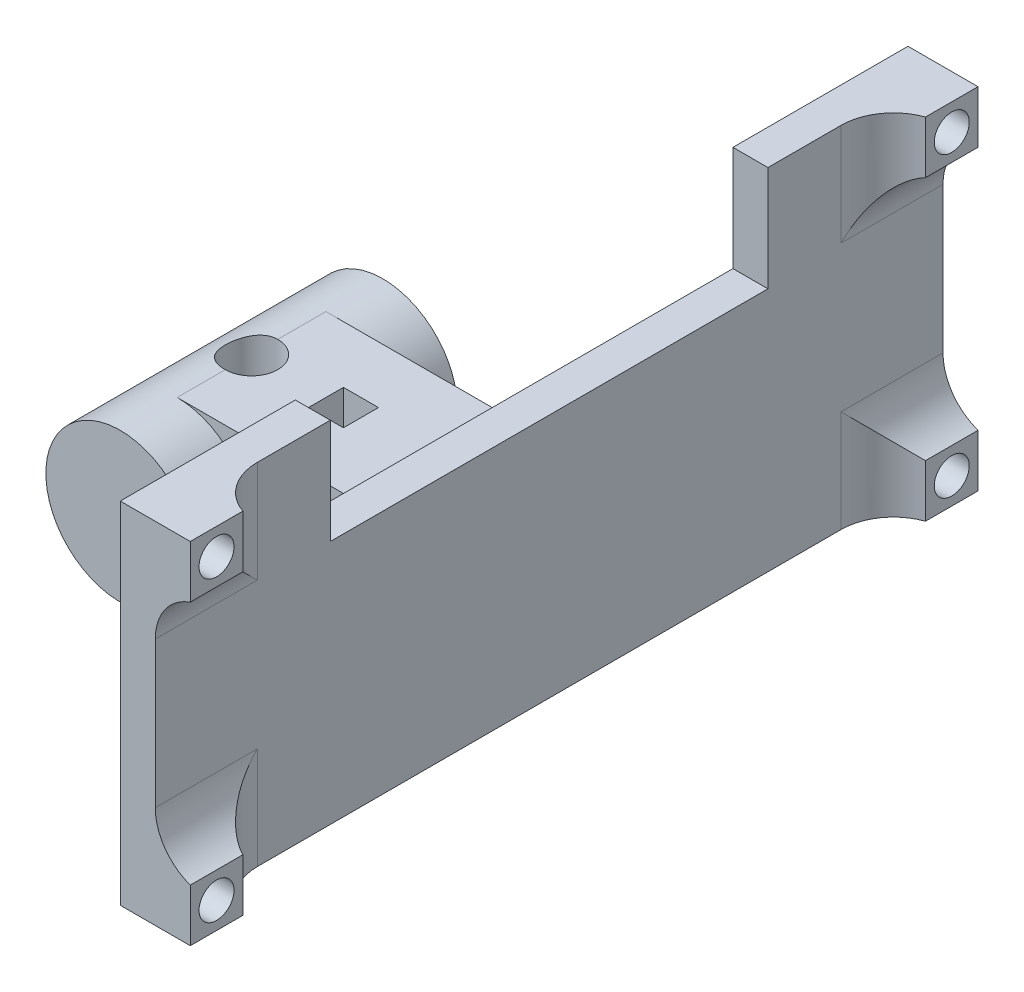
SolidWorks part; units mm, degrees
ref_plane "Front Plane" through (0, 0, 0) normal (0, 0, 1) x (1, 0, 0)
ref_plane "Top Plane" through (0, 0, 0) normal (0, 1, 0) x (1, 0, 0)
ref_plane "Right Plane" through (0, 0, 0) normal (1, 0, 0) x (0, 0, -1)
sketch "Sketch1" plane through (0, 0, 0) normal (0, 0, 1) x (1, 0, 0)
  circle A0 centre (0, 0) radius 4.25
  dimension "D1" = 8.5
extrude "Boss-Extrude1" add sketch "Sketch1" along normal mid plane 15
sketch "Sketch2" plane through (0, 0, 0) normal (1, 0, 0) x (0, 0, -1)
  line L0 (7.5, 4.25) -> (-7.5, 4.25) construction
  line L1 (7.5, 4.25) -> (-7.5, 4.25) construction
  line L3 (-4.25, -4.25) -> (4.25, -4.25)
  line L4 (-4.25, -4.25) -> (-4.25, 4.25)
  line L5 (-4.25, 4.25) -> (4.25, 4.25)
  line L6 (4.25, -4.25) -> (4.25, 4.25)
  line L7 (-4.25, -4.25) -> (4.25, 4.25) construction
  line L8 (-4.25, 4.25) -> (4.25, -4.25) construction
  point P0 (0, 0)
  dimension "D1" = 8.5
extrude "Boss-Extrude2" add sketch "Sketch2" along normal blind 15
sketch "Sketch3" plane through (15, 0, 0) normal (1, 0, 0) x (0, 0, -1)
  line L0 (-4.25, -4.25) -> (4.25, -4.25) construction
  line L1 (-22.5, -4.25) -> (22.5, -4.25)
  line L2 (-22.5, -4.25) -> (-22.5, 15.75)
  line L3 (-22.5, 15.75) -> (22.5, 15.75)
  line L4 (22.5, -4.25) -> (22.5, 15.75)
  point P6 (0, 15.75)
  dimension "D1" = 45
  dimension "D2" = 20
extrude "Boss-Extrude3" add sketch "Sketch3" along normal blind 4
sketch "Sketch4" plane through (19, 0, 0) normal (1, 0, 0) x (0, 0, -1)
  line L0 (-22.5, 5.75) -> (22.5, 5.75) construction
  line L1 (-22.5, 15.75) -> (-22.5, -4.25) construction
  line L2 (22.5, -4.25) -> (22.5, 15.75) construction
  line L3 (0, 15.75) -> (0, -4.25) construction
  line L4 (22.5, 15.75) -> (-22.5, 15.75) construction
  line L5 (-22.5, -4.25) -> (22.5, -4.25) construction
  circle A0 centre (-21, 14.25) radius 1
  circle A1 centre (-21, -2.75) radius 1
  circle A2 centre (21, -2.75) radius 1
  circle A3 centre (21, 14.25) radius 1
  dimension "D1" = 2
  dimension "D2" = 17
  dimension "D3" = 42
extrude "Cut-Extrude1" cut sketch "Sketch4" against normal through all
sketch "Sketch5" plane through (19, 0, 0) normal (1, 0, 0) x (0, 0, -1)
  line L0 (-19.5, 15.75) -> (19.5, 15.75)
  line L1 (-22.5, 15.75) -> (-19.5, 15.75)
  line L2 (-22.5, 15.75) -> (-22.5, 12.75)
  line L3 (-22.5, 12.75) -> (-19.5, 12.75)
  line L4 (-19.5, 15.75) -> (-19.5, 12.75)
  line L5 (-22.5, -4.25) -> (-19.5, -4.25)
  line L6 (-22.5, -4.25) -> (-22.5, -1.25)
  line L7 (-22.5, -1.25) -> (-19.5, -1.25)
  line L8 (-19.5, -4.25) -> (-19.5, -1.25)
  line L9 (22.5, -4.25) -> (19.5, -4.25)
  line L10 (22.5, -4.25) -> (22.5, -1.25)
  line L11 (22.5, -1.25) -> (19.5, -1.25)
  line L12 (19.5, -4.25) -> (19.5, -1.25)
  line L13 (22.5, 15.75) -> (19.5, 15.75)
  line L14 (22.5, 15.75) -> (22.5, 12.75)
  line L15 (22.5, 12.75) -> (19.5, 12.75)
  line L16 (19.5, 15.75) -> (19.5, 12.75)
  line L17 (22.5, 12.75) -> (22.5, -1.25)
  line L18 (19.5, -4.25) -> (-19.5, -4.25)
  line L19 (-22.5, -1.25) -> (-22.5, 12.75)
  line M19 (-22.5, 15.75) -> (-22.5, -4.25)
  line M20 (-22.5, -4.25) -> (22.5, -4.25)
  line M21 (22.5, -4.25) -> (22.5, 15.75)
  line M22 (22.5, 15.75) -> (-22.5, 15.75)
  dimension "D1" = 3
extrude "Cut-Extrude2" cut sketch "Sketch5" against normal blind 2 contours L16 L4 L3 L7 L8 L12 L11 L15 M22 M19 M20 M21 region at (19, 5.75, 0)
sketch "Sketch6" plane through (17, 0, 0) normal (1, 0, 0) x (0, 0, -1)
  line L0 (19.5, 15.75) -> (-19.5, 15.75) construction
  line L1 (-12.5, 15.75) -> (12.5, 15.75)
  line L2 (-12.5, 15.75) -> (-12.5, 9.75)
  line L3 (-12.5, 9.75) -> (12.5, 9.75)
  line L4 (12.5, 15.75) -> (12.5, 9.75)
  point P6 (0, 9.75)
  dimension "D1" = 25
  dimension "D2" = 6
extrude "Cut-Extrude3" cut sketch "Sketch6" against normal blind 2
sketch "Sketch7" plane through (0, 4.25, 0) normal (0, 1, 0) x (1, 0, 0)
  circle A0 centre (0, 0) radius 1.5
  dimension "D1" = 3
extrude "Cut-Extrude4" cut sketch "Sketch7" against normal through all both and the other way through all
ref_plane "Plane1" through (0, 0, 0) normal (0, 1, 0) x (1, 0, 0)
sketch "Sketch8" plane through (0, 0, 0) normal (0, 1, 0) x (1, 0, 0)
  line L0 (4.25, 4.25) -> (4.25, 7.5) construction
  line L1 (4.25, 1) -> (6.25, 1)
  line L2 (4.25, 1) -> (4.25, -1)
  line L3 (4.25, -1) -> (6.25, -1)
  line L4 (6.25, 1) -> (6.25, -1)
  point P7 (4.25, 0)
  dimension "D1" = 2
  dimension "D2" = 2
extrude "Cut-Extrude5" cut sketch "Sketch8" against normal through all both and the other way through all
fillet "Fillet1" radius 3 8 edges at (17, -1.25, -21) (17, -2.75, -19.5) (17, 14.25, -19.5) (17, 12.75, -21) (17, -2.75, 19.5) (17, -1.25, 21) (17, 14.25, 19.5) (17, 12.75, 21)
